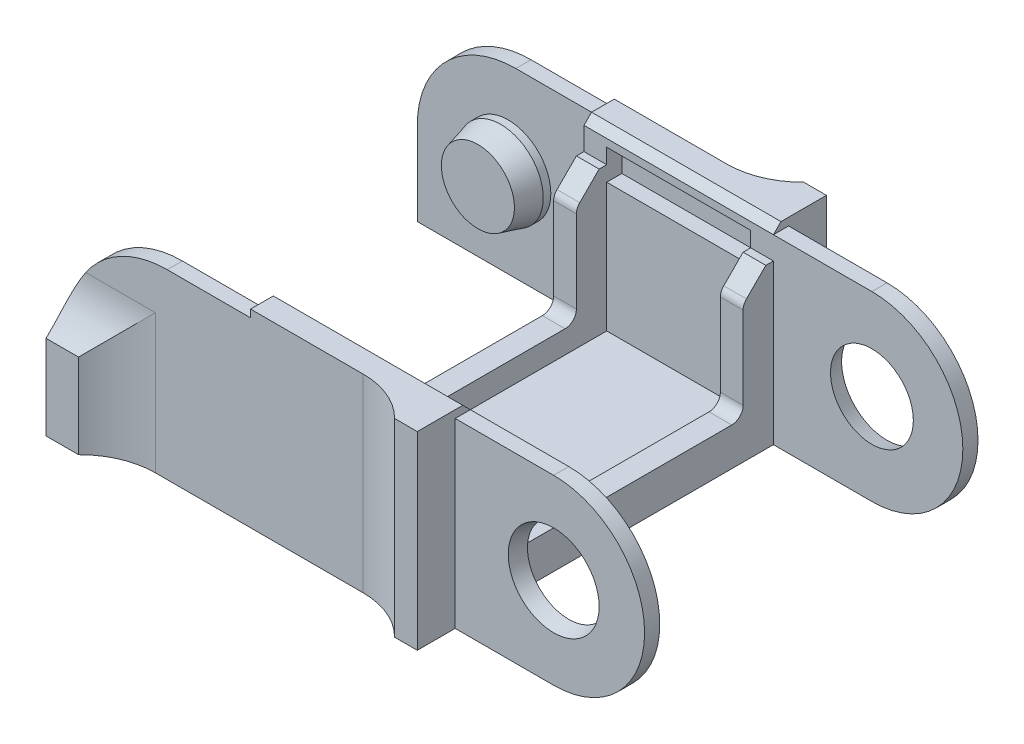
SolidWorks part; units mm, degrees
ref_plane "Front" through (0, 0, 0) normal (0, 0, 1) x (1, 0, 0)
ref_plane "Top" through (0, 0, 0) normal (0, 1, 0) x (1, 0, 0)
ref_plane "Right" through (0, 0, 0) normal (1, 0, 0) x (0, 0, -1)
sketch "Эскиз1" plane through (0, 0, 0) normal (0, 0, 1) x (1, 0, 0)
  line L1 (-38.7795, 23.7195) -> (-13.7795, 23.7195)
  line L2 (-38.7795, 23.7195) -> (-38.7795, -1.2805)
  line L3 (-38.7795, -1.2805) -> (-13.7795, -1.2805)
  line L4 (-13.7795, 23.7195) -> (-13.7795, -1.2805)
  dimension "D1" = 25
  dimension "D2" = 25
extrude "Бобышка-Вытянуть1" add sketch "Эскиз1" along normal blind 4
sketch "Эскиз2" plane through (0, 0, 0) normal (0, 0, -1) x (-1, 0, 0)
  line L0 (38.7795, 22.7195) -> (62.7795, 22.7195)
  line L1 (38.7795, 23.7195) -> (38.7795, -1.2805) construction
  line L3 (62.7795, 22.7195) -> (62.7795, -1.2805)
  line L4 (62.7795, -1.2805) -> (38.7795, -1.2805)
  line L5 (38.7795, -1.2805) -> (38.7795, 22.7195)
  dimension "D1" = 24
  dimension "D2" = 24
extrude "Бобышка-Вытянуть2" add sketch "Эскиз2" against normal blind 2
sketch "Эскиз3" plane through (0, 0, 2) normal (0, 0, 1) x (1, 0, 0)
  line L1 (-38.7795, -1.2805) -> (-62.7795, -1.2805) construction
  line L2 (-62.7795, -1.2805) -> (-62.7795, 22.7195) construction
  circle A0 centre (-50.7795, 10.7195) radius 5.625
  dimension "D2" = 11.25
  dimension "D1" = 12
  dimension "D3" = 12
extrude "Бобышка-Вытянуть3" add sketch "Эскиз3" along normal blind 4
chamfer "Фаска1" distance 3 angle 15 1 edges at (-45.1545, 10.7195, 6) first distance on face at (-45.1545, 10.7195, 6)
sketch "Эскиз4" plane through (0, 0, 6) normal (0, 0, 1) x (1, 0, 0)
  circle A1 centre (-50.7795, 10.7195) radius 13
  circle A4 centre (-50.7795, 10.7195) radius 7.5542
sketch "Эскиз5" plane through (0, 0, 4) normal (0, 0, 1) x (1, 0, 0)
  line L0 (-18.982, 10.7195) -> (-0.7795, 10.7195) construction
  line L1 (-18.982, 22.7195) -> (-0.7795, 22.7195)
  line L2 (-18.982, -1.2805) -> (-0.7795, -1.2805)
  line L3 (-13.7795, -1.2805) -> (-13.7795, 23.7195) construction
  line L4 (-38.7795, -1.2805) -> (-13.7795, -1.2805) construction
  arc A0 (-18.982, 22.7195) -> (-18.982, -1.2805) centre (-18.982, 10.7195) ccw
  arc A1 (-0.7795, -1.2805) -> (-0.7795, 22.7195) centre (-0.7795, 10.7195) ccw
  point P2 (-9.8808, 10.7195)
  dimension "D1" = 13
  dimension "D2" = 12
  dimension "D3" = 12
extrude "Бобышка-Вытянуть4" add sketch "Эскиз5" against normal blind 2
sketch "Эскиз6" plane through (0, 0, 2) normal (0, 0, -1) x (-1, 0, 0)
  circle A0 centre (0.7795, 10.7195) radius 5
  arc A1 (0.7795, 22.7195) -> (0.7795, -1.2805) centre (0.7795, 10.7195) ccw construction
extrude "Вырез-Вытянуть2" cut sketch "Эскиз6" against normal blind 10
sketch "Эскиз8" plane through (0, 0, 4) normal (0, 0, 1) x (1, 0, 0)
  line L5 (-38.7795, 3.7195) -> (-35.7795, 3.7195)
  line L6 (-38.7795, -1.2805) -> (-13.7795, -1.2805)
  line L7 (-38.7795, -1.2805) -> (-38.7795, 3.7195)
  line L9 (-13.7795, -1.2805) -> (-13.7795, 3.7195)
  line L10 (-35.7795, 3.7195) -> (-35.7795, 0.7195)
  line L11 (-35.7795, 0.7195) -> (-16.7795, 0.7195)
  line L12 (-16.7795, 0.7195) -> (-16.7795, 3.7195)
  line L13 (-16.7795, 3.7195) -> (-13.7795, 3.7195)
  line L14 (-13.7795, 22.7195) -> (-13.7795, 23.7195) construction
  dimension "D1" = 3
  dimension "D2" = 3
  dimension "D3" = 2
  dimension "D4" = 5
  dimension "D5" = 5
extrude "Бобышка-Вытянуть6" add sketch "Эскиз8" along normal blind 20
sketch "Эскиз9" plane through (0, 0, 4) normal (0, 0, 1) x (1, 0, 0)
  line L0 (-38.7795, 23.7195) -> (-38.7795, 3.7195) construction
  line L1 (-35.7795, 20.7195) -> (-16.7795, 20.7195)
  line L2 (-35.7795, 20.7195) -> (-35.7795, 17.7195)
  line L3 (-35.7795, 17.7195) -> (-16.7795, 17.7195)
  line L4 (-16.7795, 20.7195) -> (-16.7795, 17.7195)
  line L5 (-13.7795, 22.7195) -> (-13.7795, 23.7195) construction
  line L6 (-13.7795, 23.7195) -> (-38.7795, 23.7195) construction
  dimension "D1" = 3
  dimension "D2" = 3
  dimension "D3" = 3
  dimension "D4" = 6
extrude "Вырез-Вытянуть4" cut sketch "Эскиз9" against normal blind 2
chamfer "Фаска2" distance 1 angle 45 1 edges at (-26.2795, 20.7195, 4)
chamfer "Фаска3" distance 1 angle 75 1 edges at (-5.7795, 10.7195, 2) first distance on face at (-5.7795, 10.7195, 2)
fillet "Скругление1" radius 13 1 edges at (-62.7795, 22.7195, 1)
chamfer "Фаска4" distance 1 angle 45 1 edges at (-26.2795, 23.7195, 4)
sketch "Эскиз11" plane through (0, 3.7195, 0) normal (0, 1, 0) x (1, 0, 0)
  line L0 (-35.7795, -24) -> (-35.7795, -4) construction
  line L1 (-38.7795, -4) -> (-35.7795, -4)
  line L2 (-38.7795, -4) -> (-38.7795, -8)
  line L3 (-38.7795, -8) -> (-35.7795, -8)
  line L4 (-35.7795, -4) -> (-35.7795, -8)
  dimension "D1" = 4
extrude "Бобышка-Вытянуть7" add sketch "Эскиз11" along normal blind 16
pattern_linear "Линейный массив1" count 2 spacing 22 along (1, 0, 0) of "Бобышка-Вытянуть7"
chamfer "Фаска6" distance 3 angle 45 2 edges at (-15.2795, 19.7195, 8) (-37.2795, 19.7195, 8)
fillet "Скругление2" radius 1.5 4 edges at (-15.2795, 3.7195, 8) (-15.2795, 16.7195, 8) (-37.2795, 16.7195, 8) (-37.2795, 3.7195, 8)
sketch "Sketch1" plane through (0, 0, 0) normal (0, 0, -1) x (-1, 0, 0)
  line L0 (62.7795, -1.2805) -> (13.7795, -1.2805) construction
  line L1 (13.7795, 23.7195) -> (16.7795, 23.7195)
  line L2 (13.7795, 23.7195) -> (13.7795, -1.2805)
  line L3 (13.7795, -1.2805) -> (16.7795, -1.2805)
  line L4 (16.7795, 23.7195) -> (16.7795, -1.2805)
  dimension "D1" = 3
extrude "Boss-Extrude1" add sketch "Sketch1" along normal blind 3
fillet "Fillet1" radius 10 1 edges at (-16.7795, 11.2195, 0)
sketch "Sketch2" plane through (0, 0, 0) normal (0, 0, -1) x (-1, 0, 0)
  line L1 (62.7795, -1.2805) -> (58.4878, -1.2805)
  line L2 (62.7795, -1.2805) -> (62.7795, 9.8816)
  line L3 (62.7795, 9.8816) -> (58.4878, 9.8816)
  line L4 (58.4878, -1.2805) -> (58.4878, 9.8816)
extrude "Boss-Extrude2" add sketch "Sketch2" along normal blind 3
fillet "Fillet2" radius 10 2 edges at (-60.6331, 9.8816, 0) (-58.4878, 4.3006, 0)
mirror "Зеркальное отражение1" about plane through (0, 0, 24) normal (0, 0, -1) of bodies 115 109
